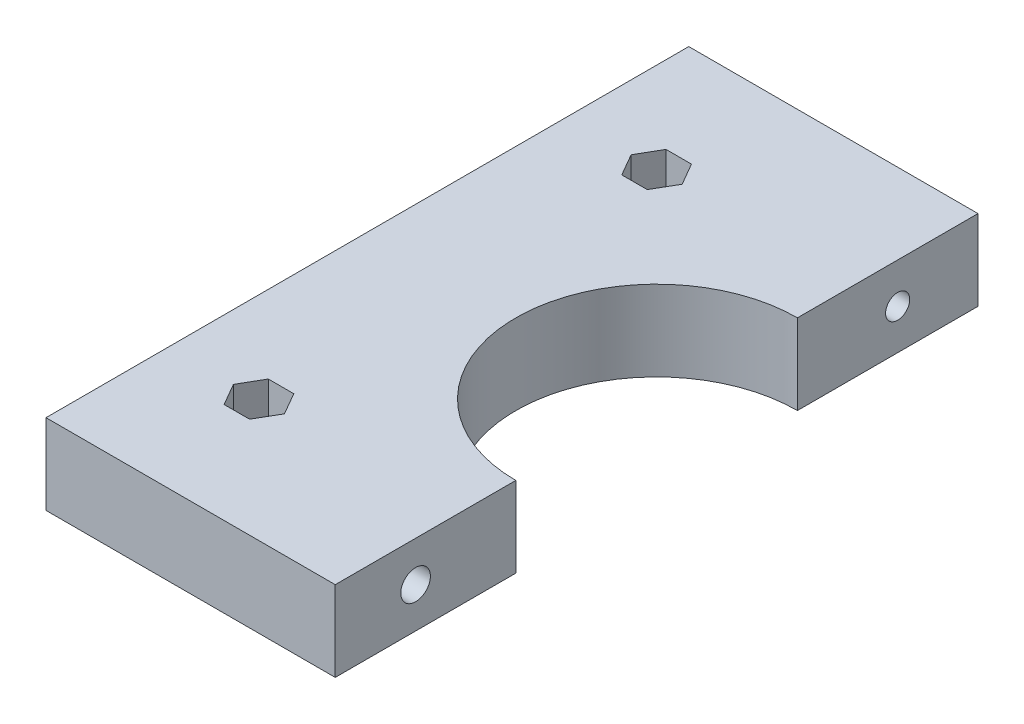
SolidWorks part; units mm, degrees
ref_plane "Front Plane" through (0, 0, 0) normal (0, 0, 1) x (1, 0, 0)
ref_plane "Top Plane" through (0, 0, 0) normal (0, 1, 0) x (1, 0, 0)
ref_plane "Right Plane" through (0, 0, 0) normal (1, 0, 0) x (0, 0, -1)
sketch "Sketch1" plane through (0, 0, 0) normal (0, 1, 0) x (1, 0, 0)
  line L0 (0, 75.8189) -> (0, -71.1446)
  line L1 (-36, -40) -> (36, -40)
  line L2 (-36, -40) -> (-36, 40)
  line L3 (-36, 40) -> (36, 40)
  line L4 (36, -40) -> (36, 40)
  line L5 (-36, -40) -> (36, 40) construction
  line L6 (-36, 40) -> (36, -40) construction
  line L7 (0, 0) -> (-44.007, 44.007)
  circle A0 centre (0, 0) radius 17.525
  circle A1 centre (-24.7487, 24.7487) radius 1.5
  circle A2 centre (24.7487, 24.7487) radius 1.5
  circle A3 centre (24.7487, -24.7487) radius 1.5
  circle A4 centre (-24.7487, -24.7487) radius 1.5
  point P0 (0, 0)
  point P21 (0, 0)
  dimension "D1" = 35.05
  dimension "D5" = 3
  dimension "D2" = 36
  dimension "D3" = 40
  dimension "D4" = 0
  dimension "D7" = 35
  dimension "D8" = 0
  dimension "D9" = 45
  dimension "D10" = 0
  dimension "D11" = 180
  dimension "D12" = 0
  dimension "D6" = 4
extrude "Boss-Extrude1" add sketch "Sketch1" along normal blind 5 and the other way blind 5 contours A0 L0 L3 L2 L1 | A1 L7 A0 L0 L3 L2 region at (-14.6089, 0, -29.4468) region at (-22.2347, 0, 11.4634)
sketch "Sketch2" plane through (0, 5, 0) normal (0, 1, 0) x (1, 0, 0)
  line L0 (-36, 40) -> (0, 40) construction
  line L1 (-23.161, 27.4987) -> (-26.3365, 27.4987)
  line L2 (-26.3365, 27.4987) -> (-27.9242, 24.7487)
  line L3 (-27.9242, 24.7487) -> (-26.3365, 21.9987)
  line L4 (-26.3365, 21.9987) -> (-23.161, 21.9987)
  line L5 (-23.161, 21.9987) -> (-21.5733, 24.7487)
  line L6 (-21.5733, 24.7487) -> (-23.161, 27.4987)
  circle A0 centre (-24.7487, 24.7487) radius 2.75 construction
  dimension "D1" = 5.5
  dimension "D2" = 0
extrude "Cut-Extrude1" cut sketch "Sketch2" against normal blind 5
mirror "Mirror1" about plane through (0, 0, 0) normal (0, 0, 1) of "Cut-Extrude1"
sketch "Sketch5" plane through (-36, 0, 0) normal (-1, 0, 0) x (0, 0, 1)
  line L0 (-40, -5) -> (-40, 5) construction
  line L1 (31.5926, 2.7475) -> (28.4172, 2.7531)
  line L2 (28.4172, 2.7531) -> (26.8246, 0.0059)
  line L3 (26.8246, 0.0059) -> (28.4074, -2.7469)
  line L4 (28.4074, -2.7469) -> (31.5828, -2.7525)
  line L5 (31.5828, -2.7525) -> (33.1754, -0.0053)
  line L6 (33.1754, -0.0053) -> (31.5926, 2.7475)
  line L7 (40, -5) -> (40, 5) construction
  circle A0 centre (-30, 0) radius 2.5
  circle A1 centre (30, 0.0003) radius 2.75 construction
  point P3 (29.9951, -2.7497)
  dimension "D1" = 5
  dimension "D2" = 5.5
  dimension "D3" = 10
  dimension "D4" = 10
extrude "Cut-Extrude3" cut sketch "Sketch5" against normal blind 30
sketch "Sketch6" plane through (-36, 0, 0) normal (-1, 0, 0) x (0, 0, 1)
  line L1 (40, -5) -> (40, 5) construction
  circle A0 centre (-30, 0) radius 1.5
  circle A1 centre (30, 0) radius 1.8433
  dimension "D1" = 3
  dimension "D2" = 10
extrude "Cut-Extrude4" cut sketch "Sketch6" against normal blind 42
